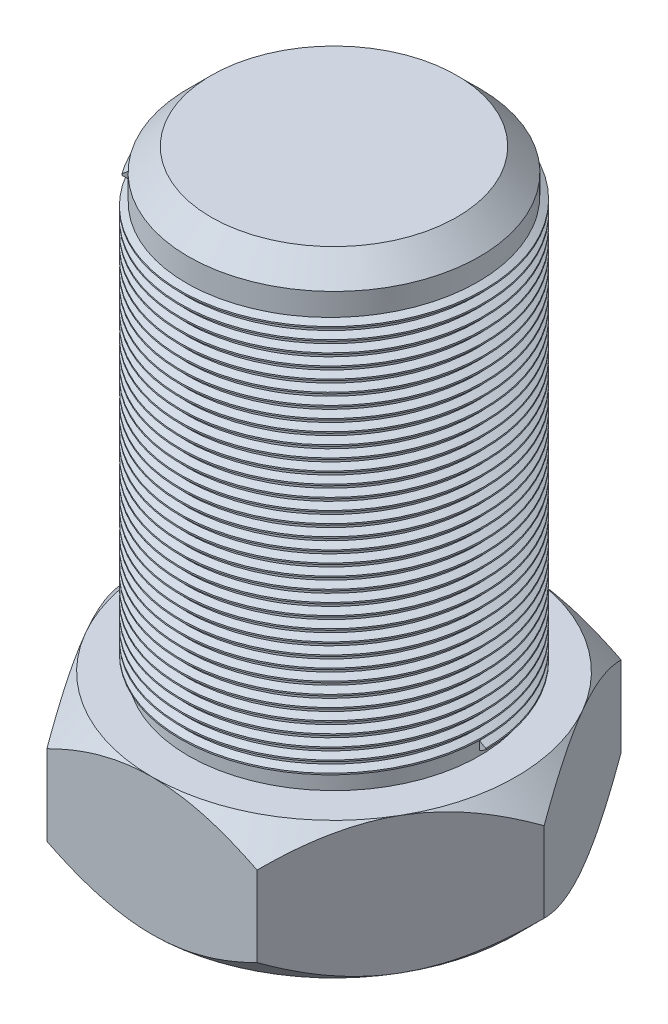
SolidWorks part; units mm, degrees
ref_plane "Front Plane" through (0, 0, 0) normal (0, 0, 1) x (1, 0, 0)
ref_plane "Top Plane" through (0, 0, 0) normal (0, 1, 0) x (1, 0, 0)
ref_plane "Right Plane" through (0, 0, 0) normal (1, 0, 0) x (0, 0, -1)
sketch "Sketch1" plane through (0, 0, 0) normal (0, 1, 0) x (1, 0, 0)
  line L1 (4.6188, 0) -> (2.3094, 4)
  line L2 (2.3094, 4) -> (-2.3094, 4)
  line L3 (-2.3094, 4) -> (-4.6188, 0)
  line L4 (-4.6188, 0) -> (-2.3094, -4)
  line L5 (-2.3094, -4) -> (2.3094, -4)
  line L6 (2.3094, -4) -> (4.6188, 0)
  circle A0 centre (0, 0) radius 4 construction
  dimension "D1" = 8
extrude "Boss-Extrude1" add sketch "Sketch1" along normal mid plane 3
sketch "Sketch2" plane through (0, 1.5, 0) normal (0, 1, 0) x (1, 0, 0)
  line L0 (-2.3094, 4) -> (-4.6188, 0) construction
  circle A0 centre (0, 0) radius 4
extrude "Cut-Extrude1" cut sketch "Sketch2" against normal through all draft 45 flip side to cut
mirror "Mirror2" about plane through (0, 0, 0) normal (0, 1, 0) of "Cut-Extrude1"
sketch "Sketch3" plane through (0, 1.5, 0) normal (0, 1, 0) x (1, 0, 0)
  circle A0 centre (0, 0) radius 3.2
extrude "Boss-Extrude2" add sketch "Sketch3" along normal blind 10 contours A0
chamfer "Chamfer1" distance 0.5 angle 45 1 edges at (0, 11.5, 3.2)
thread "Thread2" pitch 0.25 profile "Thread Profile2" start angle 0, offset 0.1, length 0, pitch 0.25, diameter 6.4
ref_plane "Plane4" through (3.2, 1.6, 0) normal (0, 0, 1) x (1, 0, 0)
sketch "Thread Profile2" plane through (3.2, 1.6, 0) normal (0, 0, 1) x (1, 0, 0)
  line L0 (0, 0) -> (0, 0.25) construction
  line L1 (0, 0) -> (0.1353, 0.0781)
  line L2 (0.1353, 0.0781) -> (0.1353, 0.1094)
  line L3 (0.1353, 0.1094) -> (0, 0.1875)
  line L4 (0.1353, 0.0937) -> (0, 0.0937) construction
  line L11 (0, 0) -> (0, 0.1875)
  point P2 (0, 0)
  dimension "Pitch" = 0.25
  dimension "Profile_Angle" = 60
  dimension "Profile_Land" = 0.0312
  dimension "Profile_Height" = 0.1353
